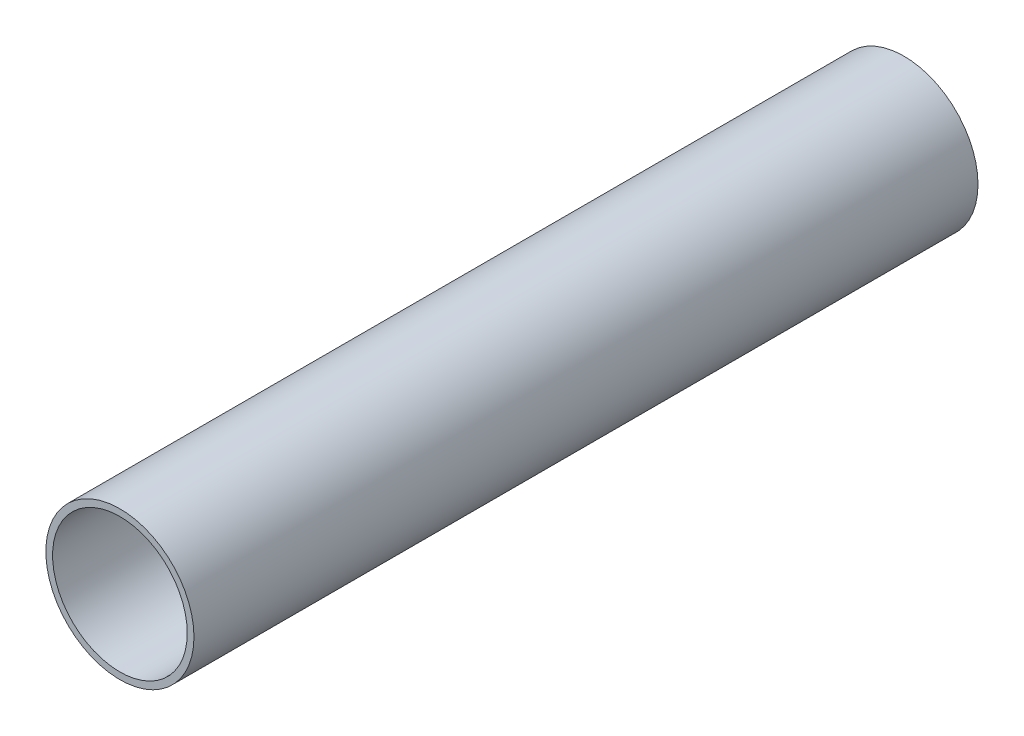
SolidWorks part; units mm, degrees
material "Carbon Fiber, Plain Weave"
ref_plane "Front Plane" through (0, 0, 0) normal (0, 0, 1) x (1, 0, 0)
ref_plane "Top Plane" through (0, 0, 0) normal (0, 1, 0) x (1, 0, 0)
ref_plane "Right Plane" through (0, 0, 0) normal (1, 0, 0) x (0, 0, -1)
ref_axis "Axis1" through (0, 0, -88.99) along (0, 0, 1)
ref_axis "Axis2" through (0, -55, 0) along (0, 1, 0)
ref_axis "Axis3" through (-88.99, 0, 0) along (1, 0, 0)
sketch "Sketch1" plane through (0, 0, 0) normal (0, 0, 1) x (1, 0, 0)
  line L0 (-74, 0) -> (74, 0)
  point P3 (0, 0)
  dimension "D1" = 148
sketch "Sketch16" plane through (0, 0, 0) normal (0, 0, 1) x (1, 0, 0)
  circle A0 centre (0, 0) radius 13.97
  circle A1 centre (0, 0) radius 12.7
  dimension "D1" = 27.94
  dimension "D2" = 25.4
extrude "Boss-Extrude1" add sketch "Sketch16" along normal mid plane 147.9
